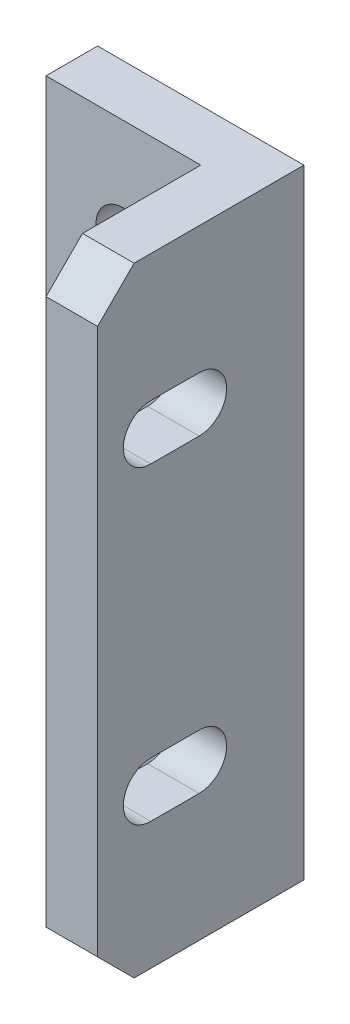
SolidWorks part; units mm, degrees
ref_plane "Front Plane" through (0, 0, 0) normal (0, 0, 1) x (1, 0, 0)
ref_plane "Top Plane" through (0, 0, 0) normal (0, 1, 0) x (1, 0, 0)
ref_plane "Right Plane" through (0, 0, 0) normal (1, 0, 0) x (0, 0, -1)
sketch "Sketch1" plane through (0, 0, 0) normal (0, 0, 1) x (1, 0, 0)
  line L1 (0, 0) -> (25.4, 0)
  line L2 (0, 0) -> (0, 76.2)
  line L3 (0, 76.2) -> (25.4, 76.2)
  line L4 (25.4, 0) -> (25.4, 76.2)
  dimension "D1" = 25.4
  dimension "D2" = 76.2
extrude "Boss-Extrude1" add sketch "Sketch1" along normal blind 6.35
sketch "Sketch2" plane through (25.4, 0, 0) normal (1, 0, 0) x (0, 0, -1)
  line L0 (-6.35, 76.2) -> (-6.35, 0)
  line L1 (-6.35, 0) -> (-20.9099, 0)
  line L2 (-20.9099, 0) -> (-25.4, 4.4901)
  line L3 (-25.4, 4.4901) -> (-25.4, 71.7099)
  line L4 (-25.4, 71.7099) -> (-20.9099, 76.2)
  line L5 (-20.9099, 76.2) -> (-6.35, 76.2)
  point P23 (0, 0)
  point P24 (-21.0521, 23.9707)
  dimension "D1" = 45
  dimension "D2" = 19.05
  dimension "D3" = 6.35
extrude "Boss-Extrude2" add sketch "Sketch2" against normal blind 6.35
hole_wizard "1/4 Clearance Slot1" positions "Sketch5" profile "Sketch4" size "1/4" standard "ANSI Inch" slot yes end condition through all
sketch "Sketch5" plane through (19.05, 0, 0) normal (-1, 0, 0) x (0, 0, 1)
  line L0 (9.525, 57.15) -> (22.225, 57.15) construction
  line L2 (6.35, 0) -> (6.35, 76.2) construction
  line L4 (15.875, 57.15) -> (15.875, 19.05) construction
  line L6 (20.9099, 0) -> (6.35, 0) construction
  point P0 (15.875, 57.15)
  point P4 (15.875, 19.05)
  point P21 (15.875, 38.1)
  dimension "D1" = 12.7
  dimension "D2" = 38.1
  dimension "D3" = 9.525
  dimension "D4" = 38.1
sketch "Sketch4" plane through (19.05, 57.15, 15.875) normal (0, 1, 0) x (0, 0, 1)
  line L0 (0, 0) -> (0, 6.35)
  line L1 (0, 6.35) -> (3.3782, 6.35)
  line L2 (3.3782, 6.35) -> (3.3782, 0)
  line L5 (3.3782, 0) -> (0, 0)
  line L11 (0, -6.35) -> (0, 107.95) construction
  dimension "Thru Hole Dia." = 6.7564
  dimension "Thru Hole Depth" = 6.35
hole_wizard "1/4 Clearance Hole1" positions "Sketch6" profile "Sketch7" hole size "1/4" standard "ANSI Inch" end condition through all
sketch "Sketch6" plane through (0, 0, 6.35) normal (0, 0, 1) x (1, 0, 0)
  line L0 (19.05, 76.2) -> (0, 76.2) construction
  line L1 (0, 0) -> (19.05, 0) construction
  point P0 (9.525, 63.5)
  point P2 (9.525, 12.7)
  point P5 (0, 0)
  point P6 (0, 0)
  point P9 (9.525, 76.2)
  point P10 (9.525, 15.133)
  dimension "D1" = 50.8
  dimension "D2" = 12.7
sketch "Sketch7" plane through (9.525, 63.5, 6.35) normal (1, 0, 0) x (0, -1, 0)
  line L0 (0, 0) -> (0, 6.35)
  line L1 (0, 6.35) -> (3.3782, 6.35)
  line L2 (3.3782, 6.35) -> (3.3782, 0)
  line L5 (3.3782, 0) -> (0, 0)
  line L11 (0, -6.35) -> (0, 107.95) construction
  dimension "Thru Hole Dia." = 6.7564
  dimension "Thru Hole Depth" = 6.35
